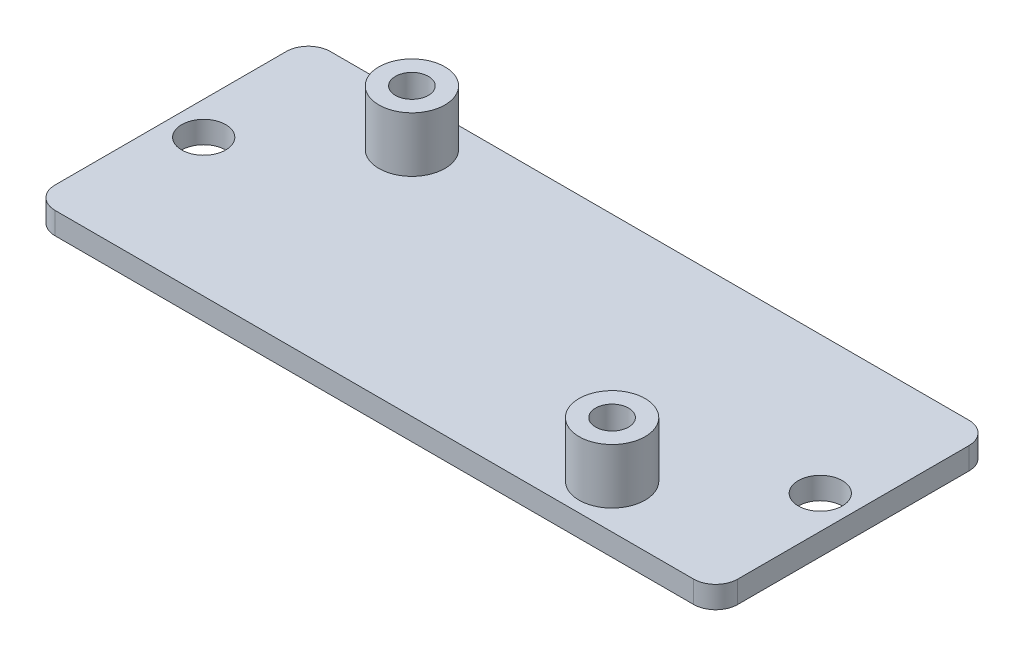
SolidWorks part; units mm, degrees
material "ABS"
ref_plane "Спереди" through (0, 0, 0) normal (0, 0, 1) x (1, 0, 0)
ref_plane "Сверху" through (0, 0, 0) normal (0, 1, 0) x (1, 0, 0)
ref_plane "Справа" through (0, 0, 0) normal (1, 0, 0) x (0, 0, -1)
sketch "Эскиз1" plane through (0, 0, 0) normal (0, 1, 0) x (1, 0, 0)
  line L1 (0, 0) -> (62, 0)
  line L2 (0, 0) -> (0, -25)
  line L3 (0, -25) -> (62, -25)
  line L4 (62, 0) -> (62, -25)
  dimension "D1" = 25
  dimension "D2" = 62
extrude "Бобышка-Вытянуть1" add sketch "Эскиз1" along normal blind 2
sketch "Эскиз2" plane through (0, 2, 0) normal (0, 1, 0) x (1, 0, 0)
  line L0 (0, 0) -> (0, -25) construction
  line L1 (62, -25) -> (62, 0) construction
  line L2 (62, 0) -> (0, 0) construction
  line L3 (0, -25) -> (62, -25) construction
  circle A0 centre (13.41, -4) radius 3
  circle A1 centre (48.59, -21) radius 3
  dimension "D2" = 13.41
  dimension "D4" = 4
  dimension "D5" = 6
  dimension "D6" = 6
  dimension "D1" = 13.41
  dimension "D3" = 4
extrude "Бобышка-Вытянуть2" add sketch "Эскиз2" along normal blind 5
sketch "Эскиз3" plane through (0, 7, 0) normal (0, 1, 0) x (1, 0, 0)
  circle A0 centre (13.41, -4) radius 1.5
  circle A1 centre (48.59, -21) radius 1.5
  dimension "D1" = 3
  dimension "D2" = 3
extrude "Вырез-Вытянуть1" cut sketch "Эскиз3" against normal through all both and the other way through all
sketch "Эскиз4" plane through (0, 2, 0) normal (0, 1, 0) x (1, 0, 0)
  line L0 (0, -12.5) -> (62, -12.5) construction
  line L1 (0, 0) -> (0, -25) construction
  line L2 (62, -25) -> (62, 0) construction
  circle A0 centre (3, -12.5) radius 2
  circle A1 centre (59, -12.5) radius 2
  dimension "D1" = 4
  dimension "D2" = 4
  dimension "D3" = 3
  dimension "D4" = 3
extrude "Вырез-Вытянуть2" cut sketch "Эскиз4" against normal through all both and the other way through all
fillet "Скругление1" radius 2 1 edges at (0, 1, 0) type face fillet first side face at (31, 1, 0) second side face at (0, 1, 12.5)
fillet "Скругление2" radius 2 1 edges at (0, 1, 25) type face fillet first side face at (0, 1, 13.5) second side face at (31, 1, 25)
fillet "Скругление3" radius 2 1 edges at (62, 1, 25) type face fillet first side face at (32, 1, 25) second side face at (62, 1, 12.5)
fillet "Скругление4" radius 2 1 edges at (62, 1, 0) type face fillet first side face at (62, 1, 11.5) second side face at (32, 1, 0)
